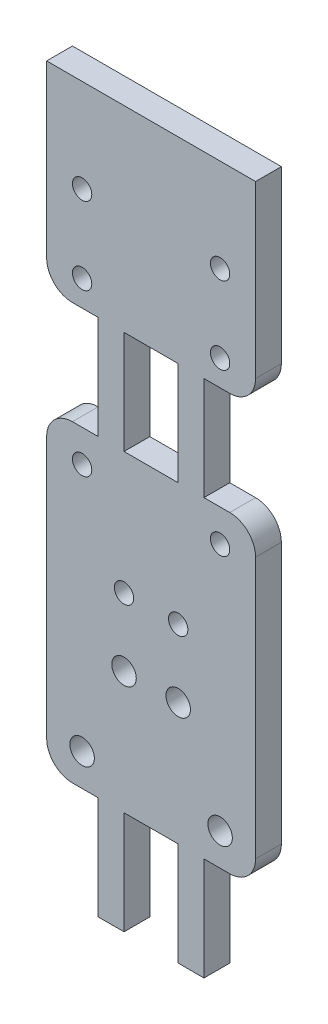
SolidWorks part; units mm, degrees
ref_plane "Front Plane" through (0, 0, 0) normal (0, 0, 1) x (1, 0, 0)
ref_plane "Top Plane" through (0, 0, 0) normal (0, 1, 0) x (1, 0, 0)
ref_plane "Right Plane" through (0, 0, 0) normal (1, 0, 0) x (0, 0, -1)
sketch "Sketch1" plane through (0, 0, 0) normal (0, 0, 1) x (1, 0, 0)
  line L0 (4, 44.7) -> (4, 52.7)
  line L1 (0, -0.06) -> (16.2, -0.06) construction
  line L2 (8.1, -0.06) -> (8.1, 67.93) construction
  line L3 (6, 12.44) -> (10.2, 12.44) construction
  line L4 (6, 20.44) -> (10.2, 20.44)
  line L5 (6, 44.7) -> (6, 52.7)
  line L6 (0, 54.7) -> (0, 67.93)
  line L7 (6, 44.7) -> (10.2, 44.7)
  line L8 (6, 52.7) -> (10.2, 52.7)
  line L9 (2, 44.7) -> (4, 44.7)
  line L10 (0, 67.93) -> (16.2, 67.93)
  line L11 (2, 20.44) -> (4, 20.44)
  line L12 (0, 22.44) -> (0, 42.7)
  line L13 (16.2, 12.44) -> (12.2, 12.44) construction
  line L14 (12.2, 20.44) -> (12.2, 12.44)
  line L15 (10.2, 12.44) -> (10.2, 20.44)
  line L16 (16.2, 12.44) -> (16.2, -0.06) construction
  line L17 (14.2, 52.7) -> (12.2, 52.7)
  line L18 (16.2, 22.44) -> (16.2, 42.7)
  line L19 (14.2, 20.44) -> (12.2, 20.44)
  line L20 (14.2, 44.7) -> (12.2, 44.7)
  line L21 (16.2, 54.7) -> (16.2, 67.93)
  line L22 (10.2, 44.7) -> (10.2, 52.7)
  line L23 (12.2, 44.7) -> (12.2, 52.7)
  line L24 (4, 12.44) -> (6, 12.44)
  line L25 (10.2, 12.44) -> (12.2, 12.44)
  line L36 (2, 52.7) -> (4, 52.7)
  line L46 (0, 12.44) -> (0, -0.06) construction
  line L47 (6, 12.44) -> (6, 20.44)
  line L48 (4, 20.44) -> (4, 12.44)
  line L49 (0, 12.44) -> (4, 12.44) construction
  circle A0 centre (2.75, 60.7) radius 0.75
  circle A1 centre (13.35, 9.94) radius 0.95 construction
  circle A2 centre (13.35, 3.94) radius 0.95 construction
  circle A3 centre (13.45, 54.7) radius 0.75
  arc A4 (16.2, 54.7) -> (14.2, 52.7) centre (14.2, 54.7) cw
  circle A5 centre (13.45, 42.2) radius 0.75
  circle A6 centre (13.45, 22.94) radius 0.95
  circle A7 centre (10.2, 29.94) radius 0.95
  arc A8 (16.2, 22.44) -> (14.2, 20.44) centre (14.2, 22.44) cw
  circle A9 centre (6, 35.2) radius 0.75
  arc A10 (14.2, 44.7) -> (16.2, 42.7) centre (14.2, 42.7) cw
  circle A11 centre (13.45, 60.7) radius 0.75
  circle A12 centre (10.2, 35.2) radius 0.75
  arc A27 (2, 44.7) -> (0, 42.7) centre (2, 42.7) ccw
  arc A31 (0, 22.44) -> (2, 20.44) centre (2, 22.44) ccw
  circle A33 centre (6, 29.94) radius 0.95
  circle A35 centre (2.75, 22.94) radius 0.95
  circle A37 centre (2.75, 42.2) radius 0.75
  arc A43 (0, 54.7) -> (2, 52.7) centre (2, 54.7) ccw
  circle A45 centre (2.75, 54.7) radius 0.75
  circle A46 centre (2.85, 3.94) radius 0.95 construction
  circle A47 centre (2.85, 9.94) radius 0.95 construction
  point P30 (8.1, 20.44)
  point P31 (8.1, 12.44)
  point P47 (8.1, 52.7)
  point P48 (8.1, 44.7)
  dimension "D10" = 1.9
  dimension "D11" = 2
  dimension "D18" = 2
  dimension "D26" = 2
  dimension "D1" = 8
  dimension "D2" = 8
  dimension "D3" = 4
  dimension "D4" = 6
  dimension "D5" = 2.5
  dimension "D6" = 4
  dimension "D9" = 2
  dimension "D12" = 2.5
  dimension "D14" = 9.5
  dimension "D16" = 2
  dimension "D17" = 2
  dimension "D19" = 2.5
  dimension "D21" = 2
  dimension "D22" = 2
  dimension "D27" = 2
  dimension "D29" = 2
  dimension "D7" = 2.85
  dimension "D8" = 2.85
  dimension "D13" = 2.75
  dimension "D15" = 6
  dimension "D20" = 2.75
  dimension "D23" = 2.75
  dimension "D28" = 6
  dimension "D30" = 2.75
  dimension "D31" = 8.1
  dimension "D32" = 15.23
  dimension "D24" = 24.26
  dimension "D25" = 9.5
  dimension "D33" = 6
extrude "Boss-Extrude1" add sketch "Sketch1" along normal blind 2
sketch "Sketch2" plane through (0, 0, 2) normal (0, 0, 1) x (1, 0, 0)
  line L0 (12.2, 12.44) -> (4, 12.44)
  line L1 (4, 20.44) -> (12.2, 20.44)
  line L2 (12.2, 20.44) -> (12.2, 12.44)
  line L3 (4, 12.44) -> (4, 20.44)
  line L4 (4, 52.7) -> (12.2, 52.7)
  line L5 (12.2, 52.7) -> (12.2, 44.7)
  line L6 (12.2, 44.7) -> (4, 44.7)
  line L7 (4, 44.7) -> (4, 52.7)
extrude "Cut-Extrude1" [suppressed] cut sketch "Sketch2" against normal up to surface (2 mm away) up to face at (3.5, 42.2, 0)
equation "\"D24@Sketch1\"= \"HL@parametersSketch@prostheticParameters.SLDPRT\" * 0.196 - 4 - 8'Thumb PIP Length"
equation "\"D32@Sketch1\" = \"HL@parametersSketch@prostheticParameters.SLDPRT\" * 0.158 - 4 - 10'Thumb DIP Length - Gap Fingertip"
equation "\"D31@Sketch1\"= \"fingerWidth@parametersSketch@prostheticParameters.SLDPRT\" / 2'Finger Width"
equation "\"D10@Sketch1\"= 1.5 + \"tol1@parametersSketch@prostheticParameters.SLDPRT\""
